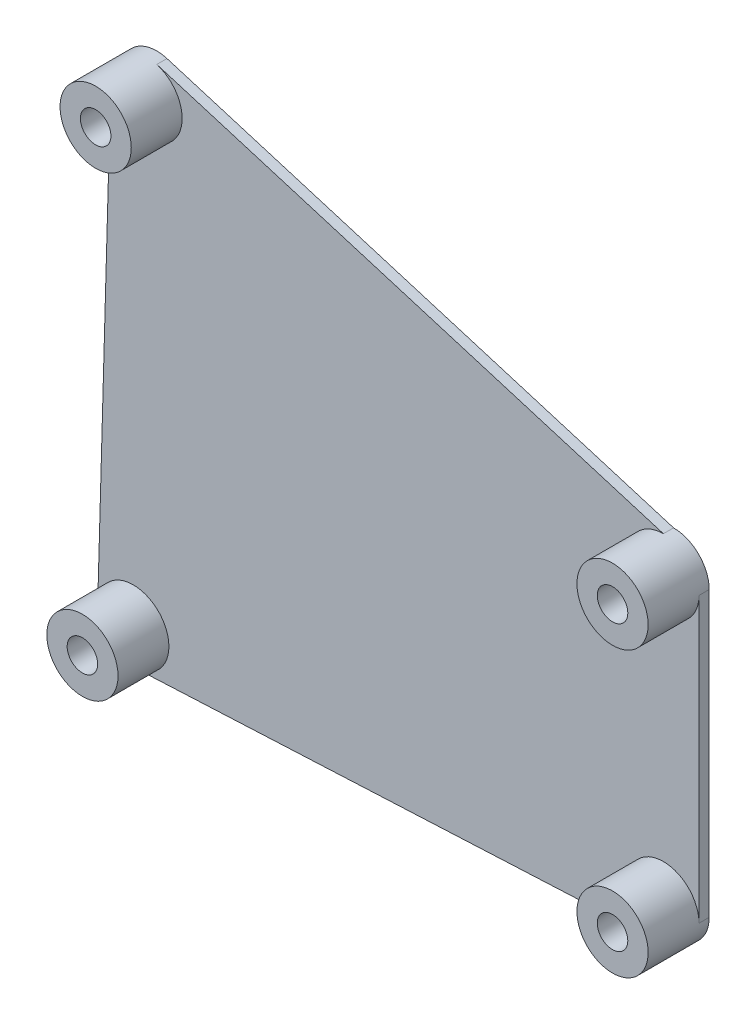
SolidWorks part; units mm, degrees
ref_plane "Front Plane" through (0, 0, 0) normal (0, 0, 1) x (1, 0, 0)
ref_plane "Top Plane" through (0, 0, 0) normal (0, 1, 0) x (1, 0, 0)
ref_plane "Right Plane" through (0, 0, 0) normal (1, 0, 0) x (0, 0, -1)
sketch "Sketch1" plane through (0, 0, 0) normal (0, 0, 1) x (1, 0, 0)
  line L0 (-2.2, 45.6) -> (-3.5, 0)
  line L1 (0, -3.5) -> (52.1, -1)
  line L2 (52.1, 33.9) -> (2.3128, 48.9503)
  line L3 (55.6, 30.4) -> (55.6, 2.5)
  circle A0 centre (0, 0) radius 1.5
  circle A1 centre (1.3, 45.6) radius 1.5
  circle A2 centre (52.1, 30.4) radius 1.5
  circle A3 centre (52.1, 2.5) radius 1.5
  circle A4 centre (0, 0) radius 3.5
  circle A5 centre (52.1, 2.5) radius 3.5
  circle A6 centre (52.1, 30.4) radius 3.5
  circle A7 centre (1.3, 45.6) radius 3.5
  dimension "D1" = 3
  dimension "D7" = 2
  dimension "D2" = 2.5
  dimension "D3" = 27.9
  dimension "D4" = 15.2
  dimension "D5" = 50.8
  dimension "D6" = 1.3
extrude "Boss-Extrude2" add sketch "Sketch1" against normal blind 6 contours A7 L0 A4 L1 A5 L3 A6 L2 | A7 A1 | A6 A2 | A5 A3 | L0 A4 L1 A0 region at (24.0106, 19.8649, 0) region at (-0.7273, 48.3307, 0) region at (0.0969, 3.3996, 0) region at (54.5049, 32.8049, 0) region at (49.6951, 4.9049, 0)
extrude "Cut-Extrude2" cut sketch "Sketch1<3>" against normal offset from surface (5 mm away) 1 contours A7 L0 A4 L1 A5 L3 A6 L2 region at (24.0106, 19.8649, 0) up to face at (26.4869, 19.6576, -6)
sketch "Sketch1<3>" plane through (0, 0, 0) normal (0, 0, 1) x (1, 0, 0) same geometry as "Sketch1"
